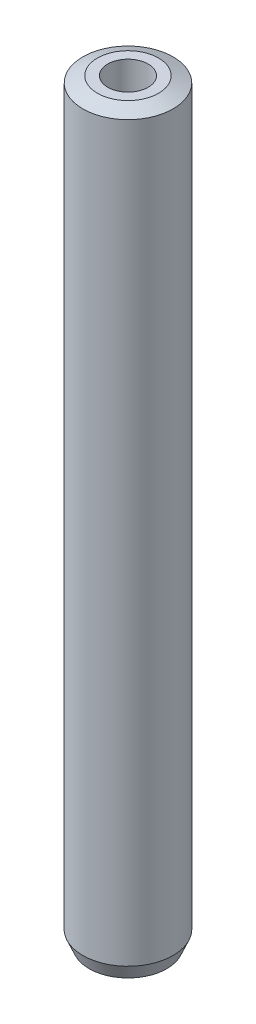
SolidWorks part; units mm, degrees
ref_plane "Front Plane" through (0, 0, 0) normal (0, 0, 1) x (1, 0, 0)
ref_plane "Top Plane" through (0, 0, 0) normal (0, 1, 0) x (1, 0, 0)
ref_plane "Right Plane" through (0, 0, 0) normal (1, 0, 0) x (0, 0, -1)
sketch "Sketch1" plane through (0, 0, 0) normal (0, 1, 0) x (1, 0, 0)
  circle A0 centre (0, 0) radius 30
  dimension "SHAFT_OD" = 60
extrude "Boss-Extrude1" add sketch "Sketch1" along normal blind 501.2864
sketch "Sketch2" plane through (0, 0, 0) normal (0, 1, 0) x (1, 0, 0)
  circle A0 centre (0, 0) radius 13.4356
  dimension "BORE_D" = 26.8711
extrude "Cut-Extrude1" cut sketch "Sketch2" along normal through all
chamfer "Chamfer1" distance 4.1414 angle 66.834 2 edges at (0, 501.2864, 30) (0, 0, 30) first distance on face at (0, 501.2864, 30) first distance on face at (0, 0, 13.4356)
